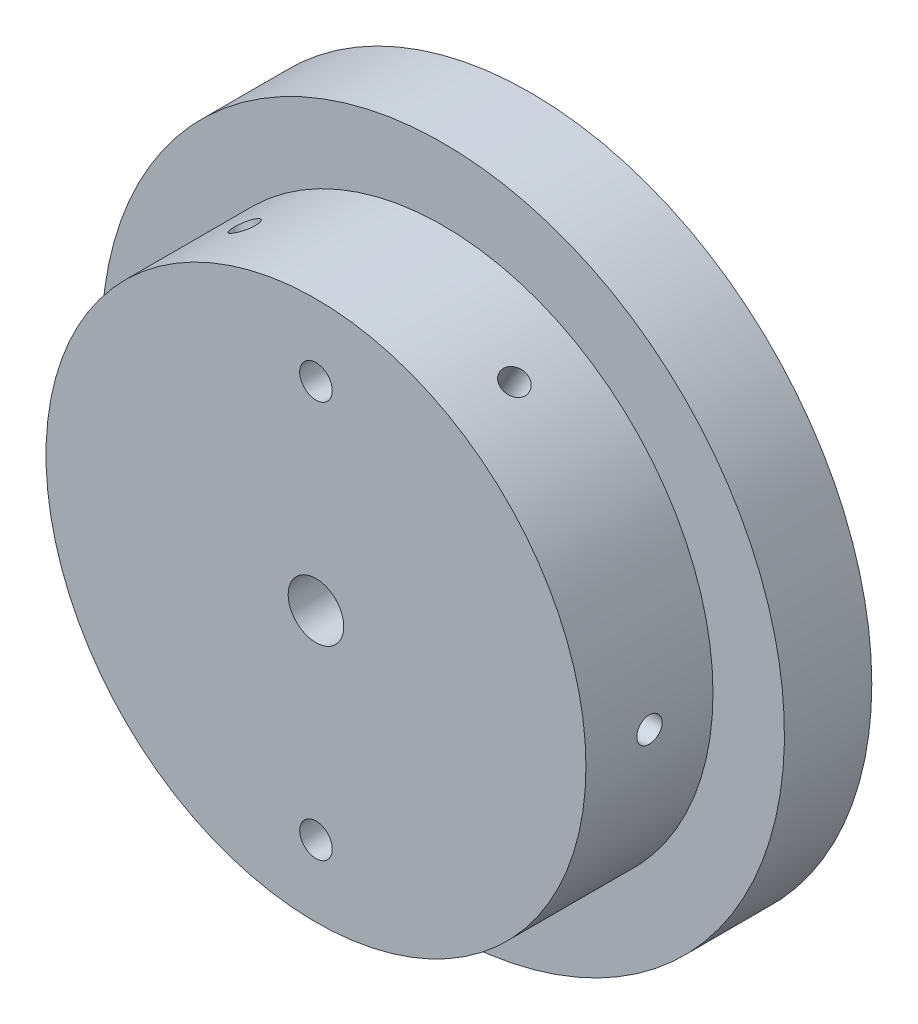
SolidWorks part; units mm, degrees
ref_plane "前视基准面" through (0, 0, 0) normal (0, 0, 1) x (1, 0, 0)
ref_plane "上视基准面" through (0, 0, 0) normal (0, 1, 0) x (1, 0, 0)
ref_plane "右视基准面" through (0, 0, 0) normal (1, 0, 0) x (0, 0, -1)
sketch "草图1" plane through (0, 0, 0) normal (0, 0, 1) x (1, 0, 0)
  circle A0 centre (0, 0) radius 17
  dimension "D1" = 34
extrude "凸台-拉伸1" add sketch "草图1" along normal blind 8 contours A0
sketch "草图2" plane through (0, 0, 0) normal (0, 0, -1) x (-1, 0, 0)
  circle A0 centre (0, 0) radius 21.5
  dimension "D1" = 43
extrude "凸台-拉伸2" add sketch "草图2" along normal blind 5.5
sketch "草图3" plane through (0, 0, -5.5) normal (0, 0, -1) x (-1, 0, 0)
  circle A0 centre (0, 0) radius 1.75
  dimension "D1" = 3.5
extrude "切除-拉伸1" cut sketch "草图3" against normal through all
sketch "草图4" plane through (0, 0, -5.5) normal (0, 0, -1) x (-1, 0, 0)
  line L1 (0, 7.5) -> (20.1494, 7.5)
  line L3 (0, -7.5) -> (20.1494, -7.5)
  arc A0 (0, 7.5) -> (0, -7.5) centre (0, 0) ccw
  circle A1 centre (0, 0) radius 21.5 construction
  arc A2 (20.1494, -7.5) -> (20.1494, 7.5) centre (0, 0) ccw
  dimension "D1" = 15
extrude "切除-拉伸2" cut sketch "草图4" against normal blind 3.5 contours A2 L1 A0 L3
sketch "草图5" plane through (0, 0, -5.5) normal (0, 0, -1) x (-1, 0, 0)
  line L0 (0, -12.5) -> (0, 12.5) construction
  line L1 (0, -12.5) -> (10, -12.5) construction
  line L2 (0, 12.5) -> (10, 12.5) construction
  line L3 (-26.3844, 0) -> (26.3844, 0) construction
  circle A1 centre (0, -12.5) radius 1.025
  circle A2 centre (0, 12.5) radius 1.025
  circle A3 centre (10, -12.5) radius 0.8
  circle A4 centre (10, 12.5) radius 0.8
  point P5 (0, 0)
  point P6 (0, 0)
  point P15 (0, 0)
  dimension "D4" = 2.05
  dimension "D5" = 1.6
  dimension "D1" = 25
  dimension "D3" = 10
extrude "切除-拉伸3" cut sketch "草图5" against normal through all contours A1 | A2 region at (0, -12.5, -5.5)
extrude "切除-拉伸4" cut sketch "草图5<3>" against normal blind 8 contours A3 | A4 region at (-10, -12.5, -5.5) region at (-10, 12.5, -5.5)
sketch "草图5<3>" plane through (0, 0, -5.5) normal (0, 0, -1) x (-1, 0, 0) same geometry as "草图5"
ref_plane "基准面4" through (17, 0, 0) normal (1, 0, 0) x (0, 0, -1)
sketch "草图6" plane through (17, 0, 0) normal (1, 0, 0) x (0, 0, -1)
  line L0 (0, 17) -> (0, -17) construction
  line L1 (-8, 17) -> (-8, -17) construction
  line L2 (0, 17) -> (0, -17) construction
  line L3 (-8, 17) -> (-8, -17) construction
  circle A0 centre (-4, 0) radius 0.8
  point P6 (0, 0)
  dimension "D1" = 1.6
  dimension "D2" = 4
extrude "切除-拉伸5" cut sketch "草图6" against normal blind 3
pattern_circular "阵列(圆周)1" count 6 over 360 about axis through (0, 0, 8) along (0, 0, -1) of "切除-拉伸5"
sketch "草图7" plane through (0, 0, -2) normal (0, 0, -1) x (-1, 0, 0)
  line L0 (0, 0) -> (10.5, 0) construction
  circle A0 centre (10.5, 0) radius 2
  dimension "D2" = 4
  dimension "10.5" = 10.5
extrude "切除-拉伸6" cut sketch "草图7" against normal blind 5
sketch "草图8" plane through (0, 0, -5.5) normal (0, 0, -1) x (-1, 0, 0)
  line L0 (0, 0) -> (-10, 0) construction
  circle A0 centre (-10, 0) radius 0.8
  dimension "D2" = 1.6
  dimension "D1" = 10
extrude "切除-拉伸7" cut sketch "草图8" against normal blind 5
